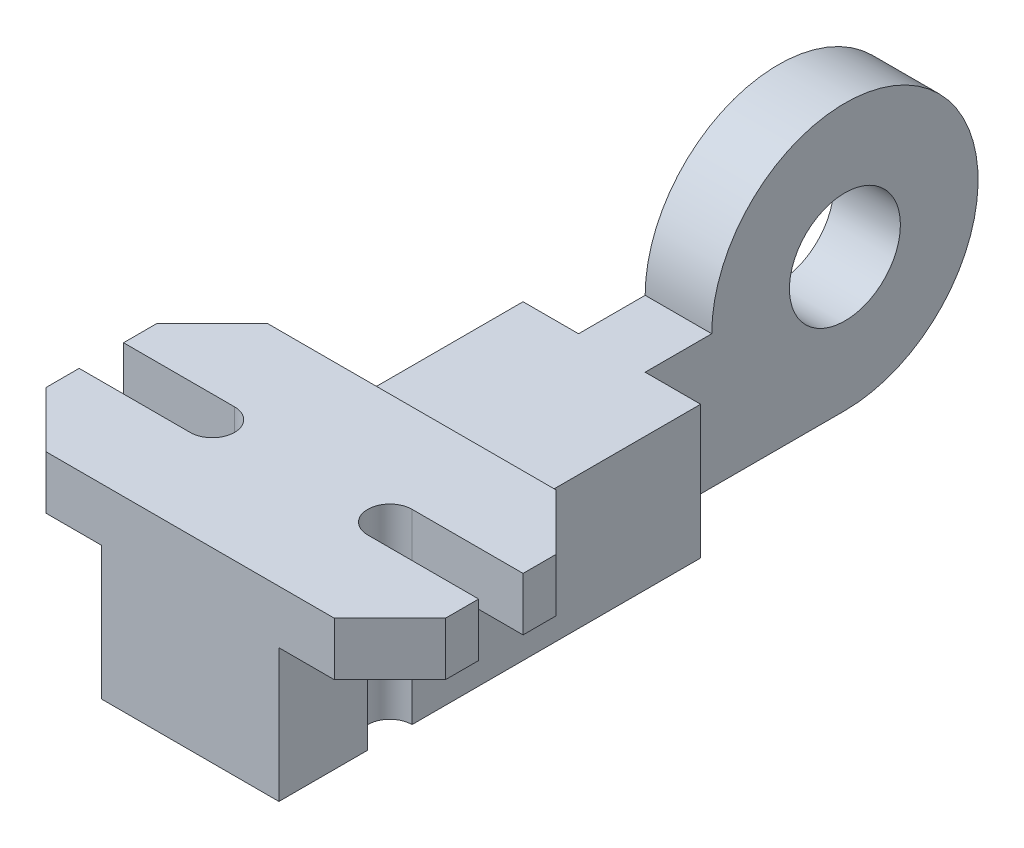
SolidWorks part; units mm, degrees
ref_plane "Front Plane" through (0, 0, 0) normal (0, 0, 1) x (1, 0, 0)
ref_plane "Top Plane" through (0, 0, 0) normal (0, 1, 0) x (1, 0, 0)
ref_plane "Right Plane" through (0, 0, 0) normal (1, 0, 0) x (0, 0, -1)
sketch "Sketch1" plane through (0, 0, 0) normal (1, 0, 0) x (0, 0, -1)
  line L1 (-46.2268, 0) -> (48.7732, 0)
  line L2 (-46.2268, 0) -> (-46.2268, 30)
  line L3 (-46.2268, 30) -> (48.7732, 30)
  line L4 (48.7732, 0) -> (48.7732, 30)
  circle A0 centre (104.3837, 15) radius 30
  point P6 (0, 0)
  point P7 (48.7732, 15)
  dimension "D1" = 95
  dimension "D2" = 30
extrude "Boss-Extrude1" add sketch "Sketch1" against normal blind 40 contours L2 L1 L4 L3
sketch "Sketch3" plane through (0, 30, 0) normal (0, 1, 0) x (1, 0, 0)
  line L0 (0, -21.2268) -> (25, -21.2268) construction
  line L1 (0, -46.2268) -> (0, 48.7732) construction
  line L2 (0, -16.2268) -> (25, -16.2268)
  line L3 (0, -26.2268) -> (25, -26.2268)
  line L4 (0, -46.2268) -> (12.4683, -46.2268)
  line L5 (12.4683, -46.2268) -> (25, -33.6951)
  line L6 (25, -33.6951) -> (25, -26.2268)
  line L7 (25, -16.2268) -> (25, -8.7585)
  line L8 (25, -8.7585) -> (12.4683, 3.7732)
  line L9 (12.4683, 3.7732) -> (0, 3.7732)
  line L10 (0, -46.2268) -> (-40, -46.2268)
  line L11 (-40, -46.2268) -> (-52.4683, -46.2268)
  line L12 (-52.4683, -46.2268) -> (-65, -33.6951)
  line L13 (-65, -33.6951) -> (-65, -26.2268)
  line L14 (-40, -21.2268) -> (-65, -21.2268) construction
  line L15 (-40, -46.2268) -> (-40, 48.7732) construction
  line L16 (-40, -26.2268) -> (-65, -26.2268)
  line L17 (-40, -16.2268) -> (-65, -16.2268)
  line L18 (-65, -16.2268) -> (-65, -8.7585)
  line L19 (-65, -8.7585) -> (-52.5, 3.7415)
  line L20 (-52.5, 3.7415) -> (-40, 3.7415)
  line L21 (-40, 3.7415) -> (0, 3.7732)
  arc A0 (0, -16.2268) -> (0, -26.2268) centre (0, -21.2268) ccw
  arc A1 (25, -26.2268) -> (25, -16.2268) centre (25, -21.2268) ccw
  arc A2 (-40, -26.2268) -> (-40, -16.2268) centre (-40, -21.2268) ccw
  arc A3 (-65, -16.2268) -> (-65, -26.2268) centre (-65, -21.2268) ccw
  point P5 (12.5, -21.2268)
  point P28 (-52.5, -21.2268)
  line M21 (0, -46.2268) -> (0, 48.7732)
  line M23 (-40, 48.7732) -> (-40, -46.2268)
  line M24 (-40, -46.2268) -> (0, -46.2268)
  dimension "D1" = 5
  dimension "D4" = 5
  dimension "D3" = 135
  dimension "D5" = 90
  dimension "D7" = 50
extrude "Boss-Extrude2" add sketch "Sketch3" along normal blind 12 contours A2 A0 L21 M23 M24 M21 | L16 L13 L12 L11 M23 | L20 L19 L18 L17 M23 | L5 L6 L3 L4 M21 | L8 L9 L2 L7 M21 region at (10.9495, 30, 7.3116) region at (-19.9978, 30, 21.2351) region at (10.9495, 30, 35.142) region at (-50.9539, 30, 7.322) region at (-50.9495, 30, 35.142)
sketch "Sketch4" plane through (0, 30, 0) normal (0, 1, 0) x (1, 0, 0)
  line L0 (0, -26.2268) -> (0, -16.2268)
  line L1 (-40, -26.2268) -> (-40, -16.2268) construction
  circle A0 centre (0, -21.2268) radius 5
  circle A1 centre (-40, -21.2268) radius 5
  line M2 (0, -26.2268) -> (0, -16.2268)
  arc M3 (0, -16.2268) -> (0, -26.2268) centre (0, -21.2268) ccw
extrude "Cut-Extrude1" cut sketch "Sketch4" against normal through all contours A1 | M3 M2 region at (-2.1221, 30, 21.2268) region at (-40, 30, 21.2268)
move or copy body "Body-Move/Copy1" bodies to move or copy 103 copy no translate (20, 0, 0) parameters "D1"=20, "D2"=0, "D3"=0
sketch "Sketch6" plane through (0, 0, 0) normal (1, 0, 0) x (0, 0, -1)
  line L0 (48.7732, 30) -> (63.7732, 30)
  line L1 (48.7732, 0) -> (93.7732, 0)
  line L2 (-16.2268, 0) -> (48.7732, 0) construction
  line L3 (48.7732, 30) -> (48.7732, 0)
  line L4 (-46.2268, 42) -> (-46.2268, 30) construction
  circle A0 centre (93.7732, 30) radius 30
  circle A1 centre (93.7732, 30) radius 12.5
  dimension "D1" = 140
extrude "Boss-Extrude3" add sketch "Sketch6" along normal mid plane 15 contours A0 L0 L3 L1 | A0 A1 region at (0, 12.5077, -60.5379) region at (0, 59.1515, -93.7732)
